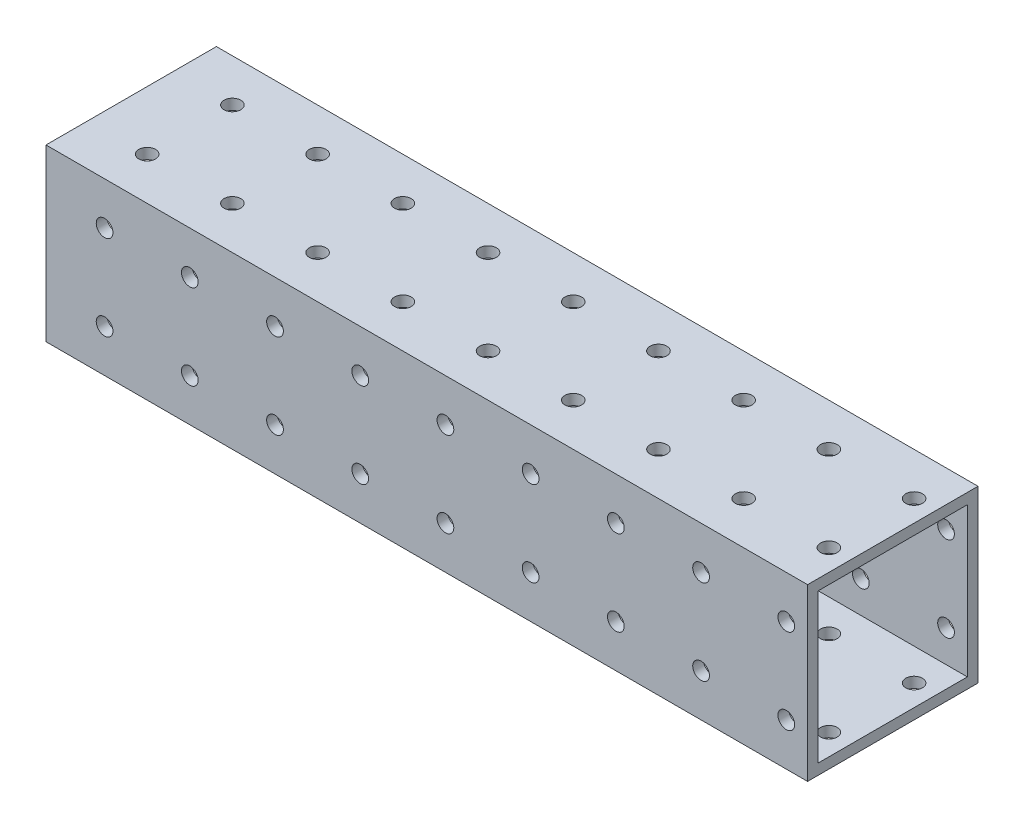
SolidWorks part; units mm, degrees
material "6061-T6 (SS)"
ref_plane "Front Plane" through (0, 0, 0) normal (0, 0, 1) x (1, 0, 0)
ref_plane "Top Plane" through (0, 0, 0) normal (0, 1, 0) x (1, 0, 0)
ref_plane "Right Plane" through (0, 0, 0) normal (1, 0, 0) x (0, 0, -1)
sketch "Sketch1" plane through (0, 0, 0) normal (1, 0, 0) x (0, 0, -1)
  line L1 (0, 0) -> (50.8, 0)
  line L2 (0, 0) -> (0, 50.8)
  line L3 (0, 50.8) -> (50.8, 50.8)
  line L4 (50.8, 0) -> (50.8, 50.8)
  dimension "D1" = 50.8
extrude "Boss-Extrude1" add sketch "Sketch1" along normal blind 227.0125
shell "Shell1" thickness 3.175 removed face at (0, 25.4, -25.4) removed face at (227.0125, 25.4, -25.4)
sketch "Sketch2" plane through (0, 0, -50.8) normal (0, 0, -1) x (-1, 0, 0)
  line L0 (-220.6625, 0) -> (-220.6625, 50.8) construction
  line L1 (-227.0125, 0) -> (0, 0) construction
  line L2 (-227.0125, 50.8) -> (0, 50.8) construction
  line L3 (-227.0125, 0) -> (-227.0125, 50.8) construction
  circle A22 centre (-220.6625, 38.1) radius 2.4892
  circle A23 centre (-220.6625, 12.7) radius 2.4892
  dimension "D2" = 4.9784
  dimension "D3" = 25.4
  dimension "D4" = 12.7
  dimension "D1" = 6.35
extrude "Cut-Extrude3" cut sketch "Sketch2" against normal through all
sketch "Sketch3" plane through (0, 0, 0) normal (0, -1, 0) x (1, 0, 0)
  line L0 (220.6625, 0) -> (220.6625, -50.8) construction
  line L1 (227.0125, 0) -> (0, 0) construction
  line L2 (227.0125, -50.8) -> (0, -50.8) construction
  line L5 (227.0125, -50.8) -> (227.0125, 0) construction
  circle A2 centre (220.6625, -12.7) radius 2.4892
  circle A3 centre (220.6625, -38.1) radius 2.4892
  dimension "D1" = 4.9784
  dimension "D2" = 12.7
  dimension "D3" = 25.4
  dimension "D4" = 6.35
extrude "Cut-Extrude2" cut sketch "Sketch3" against normal through all
pattern_linear "LPattern1" count 9 spacing 25.4 along (-1, 0, 0) of "Cut-Extrude2", "Cut-Extrude3"
